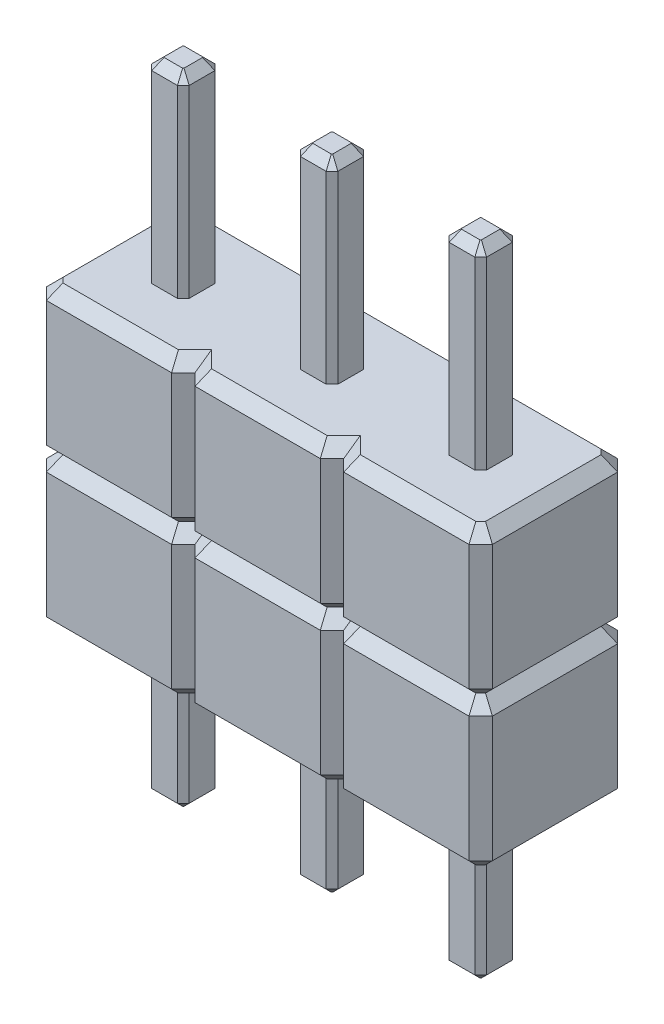
SolidWorks part; units mm, degrees
note: The reader was unsure of these and kept them because the rebuilt part matched: shared geometry of "Эскиз1<3>", "Эскиз1<4>", "Эскиз1<5>".
ref_plane "Спереди" through (0, 0, 0) normal (0, 0, 1) x (1, 0, 0)
ref_plane "Сверху" through (0, 0, 0) normal (0, 1, 0) x (1, 0, 0)
ref_plane "Справа" through (0, 0, 0) normal (1, 0, 0) x (0, 0, -1)
sketch "Эскиз1" plane through (0, 0, 0) normal (0, 1, 0) x (1, 0, 0)
  line L0 (0, 0) -> (0, 5470.6329) construction
  line L1 (0, 0) -> (-5470.6329, 0) construction
  line L2 (-1.59, 0.22) -> (-1.49, 0.32)
  line L3 (-1.49, -0.32) -> (-1.05, -0.32)
  line L4 (-1.59, -0.22) -> (-1.59, 0.22)
  line L5 (-1.49, 0.32) -> (-1.05, 0.32)
  line L6 (-0.95, -0.22) -> (-0.95, 0.22)
  line L7 (-1.59, -0.32) -> (-0.95, 0.32) construction
  line L8 (-1.59, 0.32) -> (-0.95, -0.32) construction
  line L9 (-2.34, 1.27) -> (-0.2, 1.27)
  line L10 (-2.54, 1.07) -> (-2.54, -1.07)
  line L11 (-2.34, -1.27) -> (-0.2, -1.27)
  line L12 (0, 1.07) -> (0, -1.07)
  line L13 (-2.54, 1.27) -> (0, -1.27) construction
  line L14 (-2.54, -1.27) -> (0, 1.27) construction
  line L15 (-1.05, 0.32) -> (-0.95, 0.22)
  line L16 (-1.05, -0.32) -> (-0.95, -0.22)
  line L17 (-1.59, -0.22) -> (-1.49, -0.32)
  line L18 (-2.54, 1.07) -> (-2.34, 1.27)
  line L19 (-0.2, 1.27) -> (0, 1.07)
  line L20 (-0.2, -1.27) -> (0, -1.07)
  line L21 (-2.54, -1.07) -> (-2.34, -1.27)
  line L22 (0.95, 0.22) -> (1.05, 0.32)
  line L23 (1.05, -0.32) -> (1.49, -0.32)
  line L24 (0.95, -0.22) -> (0.95, 0.22)
  line L25 (1.05, 0.32) -> (1.49, 0.32)
  line L26 (1.59, -0.22) -> (1.59, 0.22)
  line L27 (0.2, 1.27) -> (2.34, 1.27)
  line L28 (0, 1.07) -> (0, -1.07)
  line L29 (0.2, -1.27) -> (2.34, -1.27)
  line L30 (2.54, 1.07) -> (2.54, -1.07)
  line L31 (1.49, 0.32) -> (1.59, 0.22)
  line L32 (1.49, -0.32) -> (1.59, -0.22)
  line L33 (0.95, -0.22) -> (1.05, -0.32)
  line L34 (0, 1.07) -> (0.2, 1.27)
  line L35 (2.34, 1.27) -> (2.54, 1.07)
  line L36 (2.34, -1.27) -> (2.54, -1.07)
  line L37 (0, -1.07) -> (0.2, -1.27)
  line L38 (0.95, -0.32) -> (1.59, 0.32) construction
  line L39 (0.95, 0.32) -> (1.59, -0.32) construction
  line L40 (0, 1.27) -> (2.54, -1.27) construction
  line L41 (0, -1.27) -> (2.54, 1.27) construction
  line L42 (3.49, 0.22) -> (3.59, 0.32)
  line L43 (3.59, -0.32) -> (4.03, -0.32)
  line L44 (3.49, -0.22) -> (3.49, 0.22)
  line L45 (3.59, 0.32) -> (4.03, 0.32)
  line L46 (4.13, -0.22) -> (4.13, 0.22)
  line L47 (2.74, 1.27) -> (4.88, 1.27)
  line L48 (2.74, -1.27) -> (4.88, -1.27)
  line L49 (5.08, 1.07) -> (5.08, -1.07)
  line L50 (4.03, 0.32) -> (4.13, 0.22)
  line L51 (4.03, -0.32) -> (4.13, -0.22)
  line L52 (3.49, -0.22) -> (3.59, -0.32)
  line L53 (2.54, 1.07) -> (2.74, 1.27)
  line L54 (4.88, 1.27) -> (5.08, 1.07)
  line L55 (4.88, -1.27) -> (5.08, -1.07)
  line L56 (2.54, -1.07) -> (2.74, -1.27)
  line L57 (3.49, -0.32) -> (4.13, 0.32) construction
  line L58 (3.49, 0.32) -> (4.13, -0.32) construction
  line L59 (2.54, 1.27) -> (5.08, -1.27) construction
  line L60 (2.54, -1.27) -> (5.08, 1.27) construction
  point P5 (-1.27, 0)
  point P10 (-1.27, 0)
  point P31 (3.81, 0)
  point P33 (1.27, 0)
  point P38 (1.27, 0)
  point P63 (3.81, 0)
  dimension "D1" = 0.64
  dimension "D2" = 1.27
  dimension "D3" = 2
  dimension "D4" = 2
extrude "Бобышка-Вытянуть1" add sketch "Эскиз1" against normal blind 2.54 contours L4 L17 L3 L16 L6 L15 L5 L2 | L24 L33 L23 L32 L26 L31 L25 L22 | L44 L52 L43 L51 L46 L50 L45 L42
extrude "Бобышка-Вытянуть2" add sketch "Эскиз1<3>" along normal blind 8.38 contours L4 L17 L3 L16 L6 L15 L5 L2 | L24 L33 L23 L32 L26 L31 L25 L22 | L44 L52 L43 L51 L46 L50 L45 L42
sketch "Эскиз1<3>" plane through (0, 0, 0) normal (0, 1, 0) x (1, 0, 0) same geometry as "Эскиз1"
extrude "Бобышка-Вытянуть3" add sketch "Эскиз1<4>" along normal blind 2.54 contours L10 L21 L11 L20 L12 L19 L9 L18 L17 L4 L2 L5 L15 L6 L16 L3 | L12 L37 L29 L36 L30 L35 L27 L34 L33 L24 L22 L25 L31 L26 L32 L23 | L30 L56 L48 L55 L49 L54 L47 L53 L52 L44 L42 L45 L50 L46 L51 L43
sketch "Эскиз1<4>" plane through (0, 0, 0) normal (0, 1, 0) x (1, 0, 0) same geometry as "Эскиз1"
extrude "Бобышка-Вытянуть4" add sketch "Эскиз1<5>" against normal blind 2.54 from offset 5.08 separate body contours L10 L21 L11 L20 L12 L19 L9 L18 L17 L4 L2 L5 L15 L6 L16 L3 | L12 L37 L29 L36 L30 L35 L27 L34 L33 L24 L22 L25 L31 L26 L32 L23 | L30 L56 L48 L55 L49 L54 L47 L53 L52 L44 L42 L45 L50 L46 L51 L43
sketch "Эскиз1<5>" plane through (0, 0, 0) normal (0, 1, 0) x (1, 0, 0) same geometry as "Эскиз1"
chamfer "Фаска1" distance 0.15 angle 45 48 edges at (-1.54, -2.54, 0.27) (-1.27, -2.54, 0.32) (-1, -2.54, 0.27) (-0.95, -2.54, 0) (-1, -2.54, -0.27) (-1.27, -2.54, -0.32) (-1.54, -2.54, -0.27) (-1.59, -2.54, 0) (1, -2.54, 0.27) (1.27, -2.54, 0.32) (1.54, -2.54, 0.27) (1.59, -2.54, 0) (1.54, -2.54, -0.27) (1.27, -2.54, -0.32) (1, -2.54, -0.27) (0.95, -2.54, 0) (1, 8.38, -0.27) (1.27, 8.38, -0.32) (1.54, 8.38, -0.27) (1.59, 8.38, 0) (1.54, 8.38, 0.27) (1.27, 8.38, 0.32) (1, 8.38, 0.27) (0.95, 8.38, 0) (-1.54, 8.38, -0.27) (-1.27, 8.38, -0.32) (-1, 8.38, -0.27) (-0.95, 8.38, 0) (-1, 8.38, 0.27) (-1.27, 8.38, 0.32) (-1.54, 8.38, 0.27) (-1.59, 8.38, 0) (3.54, 8.38, -0.27) (3.81, 8.38, -0.32) (4.08, 8.38, -0.27) (4.13, 8.38, 0) (4.08, 8.38, 0.27) (3.81, 8.38, 0.32) (3.54, 8.38, 0.27) (3.49, 8.38, 0) (3.54, -2.54, 0.27) (3.81, -2.54, 0.32) (4.08, -2.54, 0.27) (4.13, -2.54, 0) (4.08, -2.54, -0.27) (3.81, -2.54, -0.32) (3.54, -2.54, -0.27) (3.49, -2.54, 0)
chamfer "Фаска2" distance 0.2 angle 45 20 edges at (-2.44, 2.54, -1.17) (5.08, 2.54, 0) (4.98, 2.54, -1.17) (3.81, 2.54, -1.27) (2.64, 2.54, -1.17) (2.44, 2.54, -1.17) (1.27, 2.54, -1.27) (0.1, 2.54, -1.17) (-0.1, 2.54, -1.17) (-1.27, 2.54, -1.27) (4.98, 2.54, 1.17) (3.81, 2.54, 1.27) (2.64, 2.54, 1.17) (2.44, 2.54, 1.17) (1.27, 2.54, 1.27) (0.1, 2.54, 1.17) (-0.1, 2.54, 1.17) (-1.27, 2.54, 1.27) (-2.44, 2.54, 1.17) (-2.54, 2.54, 0)
chamfer "Фаска3" distance 0.2 angle 45 44 edges at (3.49, 2.54, 0) (3.54, 2.54, -0.27) (3.81, 2.54, -0.32) (4.08, 2.54, -0.27) (4.13, 2.54, 0) (4.08, 2.54, 0.27) (3.81, 2.54, 0.32) (3.54, 2.54, 0.27) (0.95, 2.54, 0) (1, 2.54, -0.27) (1.27, 2.54, -0.32) (1.54, 2.54, -0.27) (1.59, 2.54, 0) (1.54, 2.54, 0.27) (1.27, 2.54, 0.32) (1, 2.54, 0.27) (-2.44, 2.54, 1.17) (-1.27, 2.54, 1.27) (-0.1, 2.54, 1.17) (0.1, 2.54, 1.17) (1.27, 2.54, 1.27) (2.44, 2.54, 1.17) (2.64, 2.54, 1.17) (3.81, 2.54, 1.27) (4.98, 2.54, 1.17) (5.08, 2.54, 0) (4.98, 2.54, -1.17) (3.81, 2.54, -1.27) (2.64, 2.54, -1.17) (2.44, 2.54, -1.17) (1.27, 2.54, -1.27) (0.1, 2.54, -1.17) (-0.1, 2.54, -1.17) (-1.27, 2.54, -1.27) (-2.44, 2.54, -1.17) (-2.54, 2.54, 0) (-1.59, 2.54, 0) (-1.54, 2.54, -0.27) (-1.27, 2.54, -0.32) (-1, 2.54, -0.27) (-0.95, 2.54, 0) (-1, 2.54, 0.27) (-1.27, 2.54, 0.32) (-1.54, 2.54, 0.27)
chamfer "Фаска4" distance 0.2 angle 45 20 edges at (-2.44, 0, 1.17) (-1.27, 0, 1.27) (-0.1, 0, 1.17) (0.1, 0, 1.17) (1.27, 0, 1.27) (2.44, 0, 1.17) (2.64, 0, 1.17) (3.81, 0, 1.27) (4.98, 0, 1.17) (5.08, 0, 0) (4.98, 0, -1.17) (3.81, 0, -1.27) (2.64, 0, -1.17) (2.44, 0, -1.17) (1.27, 0, -1.27) (0.1, 0, -1.17) (-0.1, 0, -1.17) (-1.27, 0, -1.27) (-2.44, 0, -1.17) (-2.54, 0, 0)
chamfer "Фаска5" distance 0.2 angle 45 20 edges at (-2.44, 5.08, -1.17) (-1.27, 5.08, -1.27) (-0.1, 5.08, -1.17) (0.1, 5.08, -1.17) (1.27, 5.08, -1.27) (2.44, 5.08, -1.17) (2.64, 5.08, -1.17) (3.81, 5.08, -1.27) (4.98, 5.08, -1.17) (5.08, 5.08, 0) (4.98, 5.08, 1.17) (3.81, 5.08, 1.27) (2.64, 5.08, 1.17) (2.44, 5.08, 1.17) (1.27, 5.08, 1.27) (0.1, 5.08, 1.17) (-0.1, 5.08, 1.17) (-1.27, 5.08, 1.27) (-2.44, 5.08, 1.17) (-2.54, 5.08, 0)
